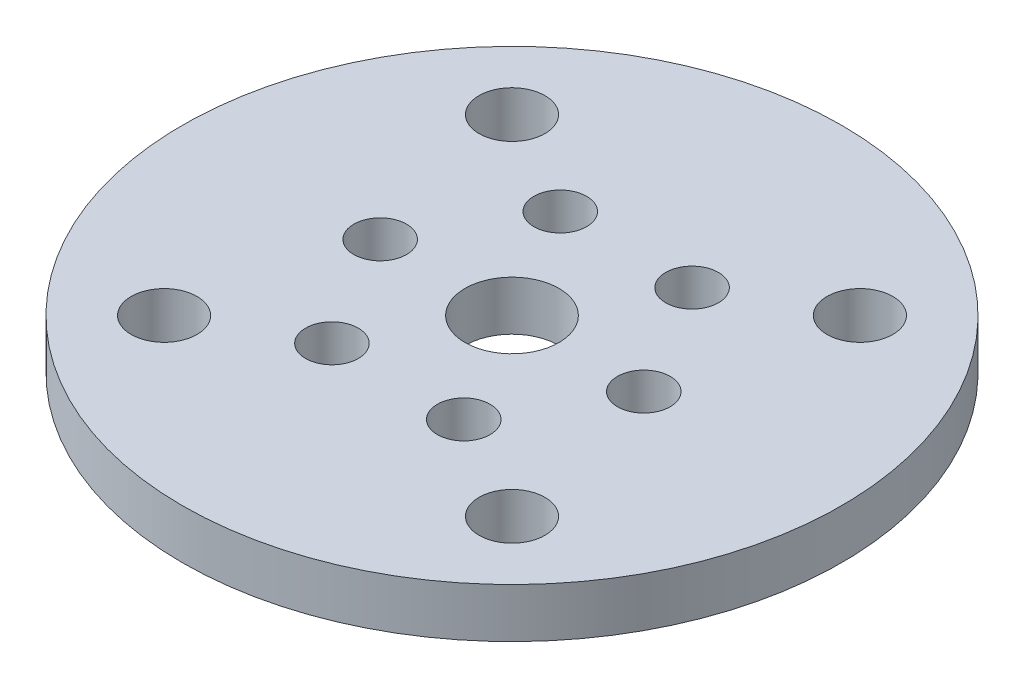
SolidWorks part; units mm, degrees
material "Policarbonato"
ref_plane "Plano frontal" through (0, 0, 0) normal (0, 0, 1) x (1, 0, 0)
ref_plane "Plano superior" through (0, 0, 0) normal (0, 1, 0) x (1, 0, 0)
ref_plane "Plano direito" through (0, 0, 0) normal (1, 0, 0) x (0, 0, -1)
ref_plane "Plano1" through (0, -3, 0) normal (0, -1, 0) x (1, 0, 0)
sketch "Esboço1" plane through (0, -3, 0) normal (0, -1, 0) x (1, 0, 0)
  circle A0 centre (0, 0) radius 2.85
  circle A1 centre (10.5571, 10.5571) radius 2
  circle A2 centre (10.5571, -10.5571) radius 2
  circle A3 centre (-10.5571, -10.5571) radius 2
  circle A4 centre (-10.5571, 10.5571) radius 2
  circle A5 centre (0, 0) radius 20
  circle A6 centre (-8, 0) radius 1.6
  circle A7 centre (-4, 6.9282) radius 1.6
  circle A8 centre (4, 6.9282) radius 1.6
  circle A9 centre (8, 0) radius 1.6
  circle A10 centre (4, -6.9282) radius 1.6
  circle A11 centre (-4, -6.9282) radius 1.6
  point P6 (7.4998, 0)
  point P14 (0, 0)
  point P15 (0, 0)
  point P26 (0, 0)
  point P28 (-4, -6.9282)
  dimension "D1" = 4
  dimension "D2" = 40
  dimension "D3" = 5.7
  dimension "D8" = 3.2
  dimension "D4" = 14.93
  dimension "D7" = 16
  dimension "D5" = 4
  dimension "D6" = 6
extrude "Ressalto-extrusão1" add sketch "Esboço1" against normal blind 3
